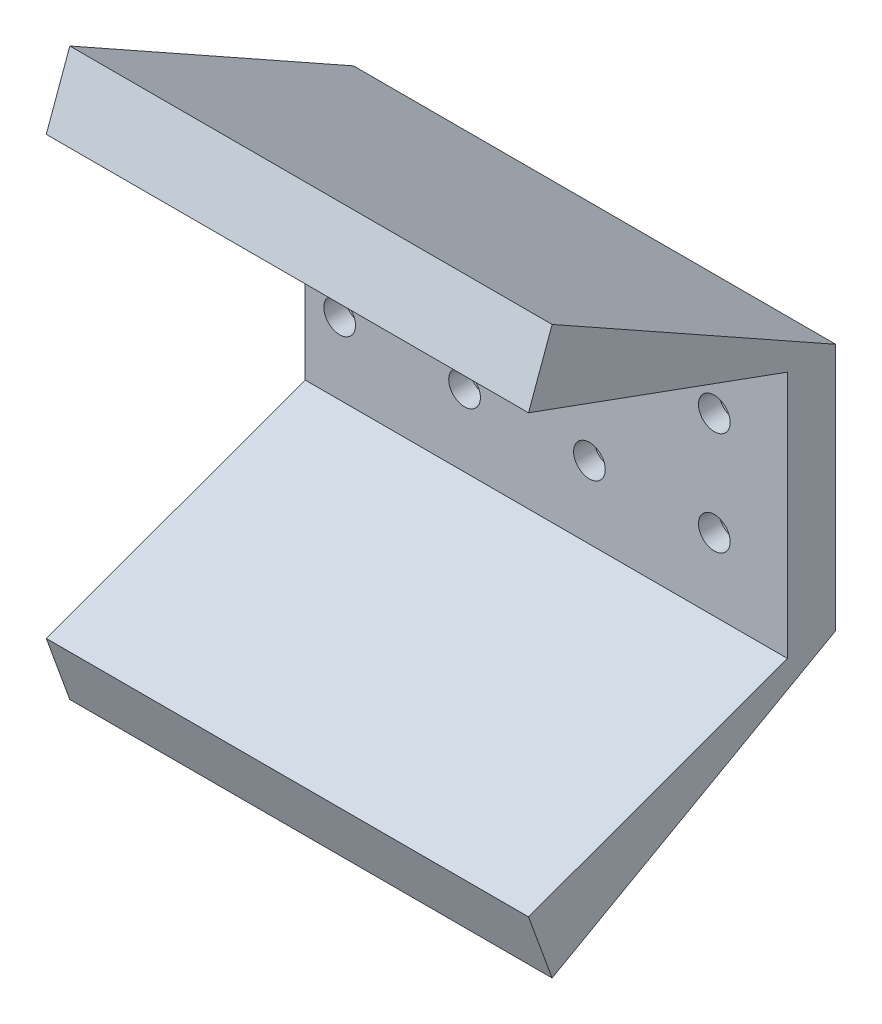
SolidWorks part; units mm, degrees
ref_plane "Plan de face" through (0, 0, 0) normal (0, 0, 1) x (1, 0, 0)
ref_plane "Plan de dessus" through (0, 0, 0) normal (0, 1, 0) x (1, 0, 0)
ref_plane "Plan de droite" through (0, 0, 0) normal (1, 0, 0) x (0, 0, -1)
sketch "Esquisse1" plane through (0, 0, 0) normal (0, 0, 1) x (1, 0, 0)
  line L0 (0, 0) -> (70, 0)
  line L1 (0, 0) -> (0, 36)
  line L2 (70, 0) -> (70, 36)
  line L3 (0, 36) -> (70, 36)
  line L4 (0, 25.5) -> (70, 25.5) construction
  line L5 (0, 10.5) -> (70, 10.5) construction
  line L6 (5, 25.5) -> (5, 10.5) construction
  line L8 (23.125, 25.5) -> (23.125, 10.5) construction
  line L10 (41.25, 25.5) -> (41.25, 10.5) construction
  line L12 (59.375, 25.5) -> (59.375, 10.5) construction
  circle A0 centre (5, 25.5) radius 2.3
  circle A1 centre (5, 10.5) radius 2.3
  circle A2 centre (23.125, 25.5) radius 2.3
  circle A3 centre (23.125, 10.5) radius 2.3
  circle A4 centre (41.25, 25.5) radius 2.3
  circle A5 centre (41.25, 10.5) radius 2.3
  circle A6 centre (59.375, 25.5) radius 2.3
  circle A7 centre (59.375, 10.5) radius 2.3
  point P27 (88.4633, 37.9035)
  dimension "D9" = 4.6
  dimension "D1" = 10.5
  dimension "D2" = 15
  dimension "D3" = 36
  dimension "D4" = 70
  dimension "D5" = 5
  dimension "D6" = 18.125
  dimension "D7" = 18.125
  dimension "D8" = 18.125
extrude "Boss.-Extru.1" add sketch "Esquisse1" along normal blind 7
sketch "Esquisse2" plane through (0, 0, 0) normal (0, 0, -1) x (-1, 0, 0)
  circle A0 centre (-59.375, 25.5) radius 4
  circle A1 centre (-41.25, 25.5) radius 4
  circle A2 centre (-23.125, 25.5) radius 4
  circle A3 centre (-5, 25.5) radius 4
  circle A4 centre (-5, 10.5) radius 4
  circle A5 centre (-23.125, 10.5) radius 4
  circle A6 centre (-41.25, 10.5) radius 4
  circle A7 centre (-59.375, 10.5) radius 4
  dimension "D1" = 8
extrude "Enlèv. mat.-Extru.1" cut sketch "Esquisse2" against normal blind 4
sketch "Esquisse3" plane through (70, 0, 0) normal (1, 0, 0) x (0, 0, -1)
  line L0 (-7, 36) -> (-44.5877, 49.6808)
  line L1 (-44.5877, 49.6808) -> (-41.1675, 59.0777)
  line L2 (-41.1675, 59.0777) -> (0, 36)
  line L3 (-7, 0) -> (-44.5877, -13.6808)
  line L4 (-44.5877, -13.6808) -> (-41.1675, -23.0777)
  line L5 (-41.1675, -23.0777) -> (0, 0)
  line L6 (-7, 0) -> (-7, 36) construction
  line L7 (-6.5294, 0) -> (0, 0)
  line L8 (-7, 0) -> (0, 0) construction
  line L9 (0, 36) -> (-7, 36)
  line L10 (-34.1519, 18) -> (-7, 18) construction
  circle A0 centre (-34.1519, 18) radius 21
  point P19 (-28.9146, 18)
  point P21 (-34.1519, 18)
  line M8 (0, 36) -> (-7, 36)
  line M10 (-7, 0) -> (0, 0)
  dimension "D7" = 42
  dimension "D1" = 10
  dimension "D2" = 10
  dimension "D3" = 110
  dimension "D4" = 110
  dimension "D5" = 40
  dimension "D6" = 40
extrude "Boss.-Extru.2" add sketch "Esquisse3" against normal blind 70 contours L2 L1 L0 M8 | L4 L5 L3 M10 region at (70, 46.941, 26.6428) region at (70, -10.941, 26.6428)
